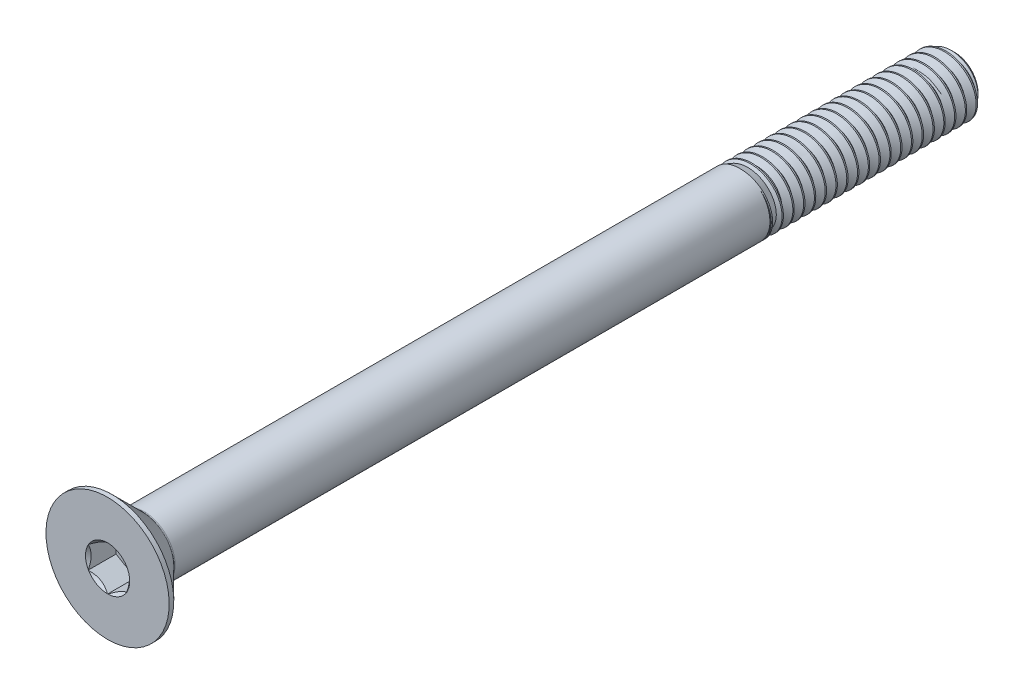
SolidWorks part; units mm, degrees
material "Plain Carbon Steel"
ref_plane "Front Plane" through (0, 0, 0) normal (0, 0, 1) x (1, 0, 0)
ref_plane "Top Plane" through (0, 0, 0) normal (0, 1, 0) x (1, 0, 0)
ref_plane "Right Plane" through (0, 0, 0) normal (1, 0, 0) x (0, 0, -1)
sketch "Sketch1" plane through (0, 0, 0) normal (0, 0, 1) x (1, 0, 0)
  line L1 (-1.25, 0.7217) -> (-1.25, -0.7217) construction
  line L2 (-1.25, -0.7217) -> (0, -1.4434) construction
  line L3 (0, -1.4434) -> (1.25, -0.7217) construction
  line L4 (1.25, -0.7217) -> (1.25, 0.7217) construction
  line L5 (1.25, 0.7217) -> (0, 1.4434) construction
  line L6 (0, 1.4434) -> (-1.25, 0.7217) construction
  circle A0 centre (0, 0) radius 4 construction
  circle A1 centre (0, 0) radius 1.25 construction
  circle A2 centre (0, 0) radius 1.435 construction
  point P11 (0, 4)
  dimension "Head Diameter" = 8
  dimension "Hex Countersink" = 2.87
  dimension "Drive Size" = 2.5
sketch "Sketch2" plane through (0, 0, 0) normal (1, 0, 0) x (0, 0, -1)
  line L0 (0, 0) -> (55, 0) construction
  line L1 (0.3, 4) -> (2.3, 2) construction
  line L2 (55, 2) -> (41, 2) construction
  line L3 (0.3, 4) -> (0, 4) construction
  line L4 (0, 4) -> (0, -4) construction
  line L5 (0, 0) -> (0, 4) construction
  line L6 (0.3, -4) -> (2.3, -2) construction
  line L7 (55, 2) -> (55, -2) construction
  line L8 (54.9562, 2.0758) -> (55.6562, 2.0758) construction
  line L9 (55.6562, 2.0758) -> (55.3062, 1.4696) construction
  line L10 (55.3062, 1.4696) -> (54.9562, 2.0758) construction
  line L11 (54.9781, 2.0379) -> (55.6344, 2.0379) construction
  line L12 (55, 2) -> (55.6125, 2) construction
  line L13 (55.2625, 1.5453) -> (55.35, 1.5453) construction
  line L14 (55.3062, 2.0758) -> (55.3062, 2) construction
  line L15 (55.3062, 1.5453) -> (55.3062, 1.4696) construction
  point P16 (55, 0)
  point P20 (1.8, 0)
  point P27 (55.3062, 2.0379)
  point P28 (52.55, -2)
  dimension "Edge Length" = 0.3
  dimension "Countersink Angle" = 90
  dimension "Head Height" = 2.3
  dimension "Thread Size" = 4
  dimension "Minimum Thread Length" = 14
  dimension "Length" = 55
  dimension "D1" = 60
  dimension "Thread Pitch" = 0.7
  dimension "D2" = 0.0875
  dimension "Hex Drive Depth" = 1.8
  dimension "D3" = 2.45
sketch "Sketch3" plane through (0, 0, 0) normal (1, 0, 0) x (0, 0, -1)
  line L0 (0.3, 4) -> (2.3, 2) construction
  line L1 (2.3, 2) -> (41, 2) construction
  line L2 (0, 0) -> (55, 0) construction
  arc A0 (2.2414, 2.0586) -> (2.3828, 2) centre (2.3828, 2.2) ccw construction
  point P8 (6.3, 0)
  point P9 (37, 0)
  dimension "Head Radius" = 0.2
  dimension "D1" = 4
  dimension "D2" = 4
sketch "Sketch4" plane through (0, 0, 0) normal (1, 0, 0) x (0, 0, -1)
  line L0 (2.3, 2) -> (0.3, 4)
  line L1 (0.3, 4) -> (0, 4)
  line L2 (0, 4) -> (0, 0)
  line L3 (0, 0) -> (55, 0)
  line L4 (55, 2) -> (55, -2) construction
  line L5 (55, 0) -> (55, 1.51)
  line L6 (55, 1.51) -> (54.51, 2)
  line L7 (55, 2) -> (41, 2) construction
  line L8 (54.51, 2) -> (2.3, 2)
  line L9 (0.3, 4) -> (2.3, 2) construction
  dimension "D1" = 45
  dimension "D2" = 0.49
revolve "Revolve1" add sketch "Sketch4" angle 360 about L0
sketch "Sketch5" plane through (0, 0, 0) normal (0, 0, 1) x (1, 0, 0)
  line L0 (-1.25, 0.7217) -> (-1.25, -0.7217) construction
  line L1 (-1.25, 0.7217) -> (-1.25, -0.7217)
  line L2 (-1.25, -0.7217) -> (0, -1.4434)
  line L3 (0, -1.4434) -> (1.25, -0.7217)
  line L4 (1.25, -0.7217) -> (1.25, 0.7217)
  line L5 (1.25, 0.7217) -> (0, 1.4434)
  line L6 (0, 1.4434) -> (-1.25, 0.7217)
  circle A0 centre (0, 0) radius 1.25 construction
  circle A1 centre (0, 0) radius 1.25 construction
extrude "Cut-Extrude1" cut sketch "Sketch5" against normal up to vertex (1.8 mm away) up to point (0, 0, -1.8)
sketch "Sketch6" plane through (0, 0, 0) normal (0, 0, 1) x (1, 0, 0)
  circle A0 centre (0, 0) radius 1.435
  circle A1 centre (0, 0) radius 1.435 construction
extrude "Cut-Extrude2" cut sketch "Sketch6" against normal up to vertex (1.8 mm away) draft 45 up to point (0, 0, -1.8)
fillet "Fillet1" radius 0.2 1 edges at (0, -2, -2.3)
sketch "Sketch7" plane through (0, 0, 0) normal (1, 0, 0) x (0, 0, -1)
  line L0 (54.9781, 2.0379) -> (55.6344, 2.0379)
  line L1 (55.6344, 2.0379) -> (55.35, 1.5453)
  line L2 (55.35, 1.5453) -> (55.2625, 1.5453)
  line L3 (55.2625, 1.5453) -> (54.9781, 2.0379)
sketch "Sketch8" plane through (0, 0, -55) normal (0, 0, -1) x (-1, 0, 0)
  circle A0 centre (0, 0) radius 2
curve "Helix/Spiral1" pitch 0.7 height 14.7 radius 2 centre (0, 0, -55) axis (0, 0, 1) start towards (0, 1, 0)
sweep "Cut-Sweep1" cut profiles "Sketch7" path "Helix/Spiral1" align with end faces yes
ref_plane "Plane1" through (0, 0, -41) normal (0, 0, 1) x (1, 0, 0)
sketch "Sketch9" plane through (0, 0, -41) normal (0, 0, 1) x (1, 0, 0)
  circle A0 centre (0, 0) radius 2
extrude "Boss-Extrude1" add sketch "Sketch9" along normal blind 1.4 and the other way blind 2.1 draft 20
equation "\"D2@Sketch2\"=\"Thread Pitch@Sketch2\"/8"
equation "\"D2@Sketch4\"=\"Thread Pitch@Sketch2\"*.7"
equation "\"D4@Helix/Spiral1\"=\"Thread Pitch@Sketch2\""
equation "\"D3@Helix/Spiral1\"=\"Minimum Thread Length@Sketch2\"+\"Thread Pitch@Sketch2\""
equation "\"D2@Boss-Extrude1\"=\"Thread Pitch@Sketch2\"*3"
equation "\"D1@Boss-Extrude1\"=\"Thread Pitch@Sketch2\"*2"
equation "\"D3@Sketch2\"=\"Thread Pitch@Sketch2\"*3.5"
equation "\"D1@Fillet1\"=\"Head Radius@Sketch3\""
equation "\"D2@Sketch3\"=\"D1@Sketch3\""
equation "\"D1@Sketch3\"=if(\"Length@Sketch2\"<25,1,4)"
